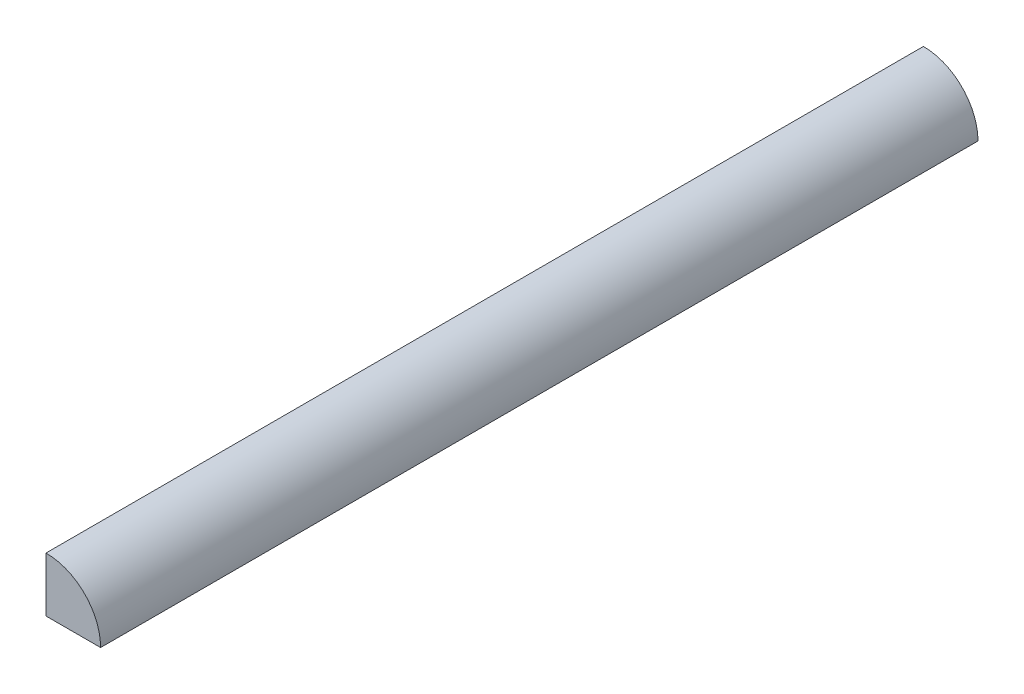
SolidWorks part; units mm, degrees
ref_plane "Plan de face" through (0, 0, 0) normal (0, 0, 1) x (1, 0, 0)
ref_plane "Plan de dessus" through (0, 0, 0) normal (0, 1, 0) x (1, 0, 0)
ref_plane "Plan de droite" through (0, 0, 0) normal (1, 0, 0) x (0, 0, -1)
sketch "Esquisse1" plane through (0, 0, 0) normal (0, 0, 1) x (1, 0, 0)
  line L1 (0, 0) -> (28, 0)
  line L2 (0, 0) -> (0, -28)
  line L3 (0, -28) -> (28, -28)
  line L4 (28, 0) -> (28, -28)
  dimension "D1" = 28
  dimension "D2" = 28
extrude "Boss.-Extru.1" add sketch "Esquisse1" along normal blind 450
fillet "Congé1" radius 28 1 edges at (28, 0, 225) type face fillet first side face at (14, 0, 225) second side face at (28, -14, 225)
